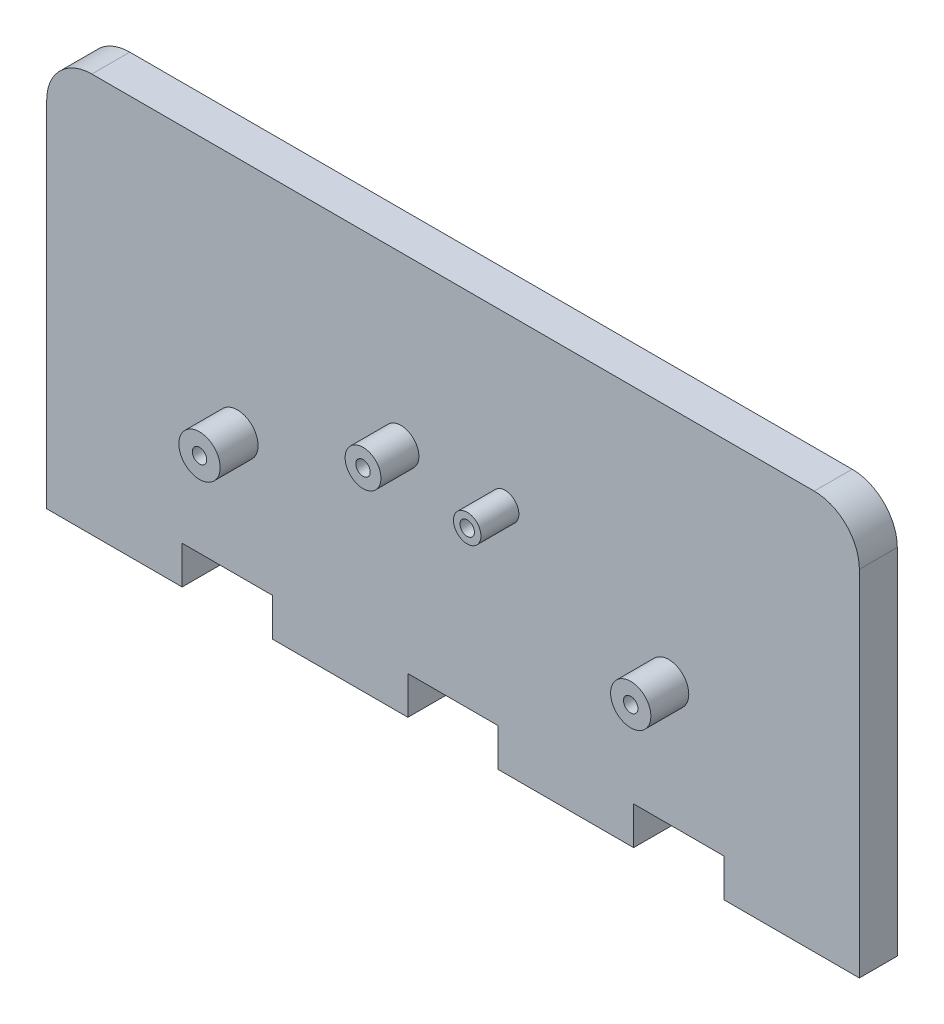
SolidWorks part; units mm, degrees
material "Teak"
ref_plane "Front Plane" through (0, 0, 0) normal (0, 0, 1) x (1, 0, 0)
ref_plane "Top Plane" through (0, 0, 0) normal (0, 1, 0) x (1, 0, 0)
ref_plane "Right Plane" through (0, 0, 0) normal (1, 0, 0) x (0, 0, -1)
sketch "Sketch1" plane through (0, 0, 0) normal (0, 0, 1) x (1, 0, 0)
  line L1 (-30.5325, 25.3111) -> (83.7675, 25.3111)
  line L2 (-30.5325, 25.3111) -> (-30.5325, -30.8229)
  line L3 (-30.5325, -30.8229) -> (83.7675, -30.8229)
  line L4 (83.7675, 25.3111) -> (83.7675, -30.8229)
  dimension "D1" = 56.134
  dimension "D2" = 114.3
extrude "Boss-Extrude1" add sketch "Sketch1" along normal blind 5.334 contours L1 L4 L3 L2
sketch "Sketch2" plane through (0, 0, 5.334) normal (0, 0, 1) x (1, 0, 0)
  line L0 (-30.5325, -30.8229) -> (83.7675, -30.8229) construction
  line L1 (-11.4825, -30.8229) -> (1.2175, -30.8229)
  line L2 (-11.4825, -30.8229) -> (-11.4825, -25.4889)
  line L3 (-11.4825, -25.4889) -> (1.2175, -25.4889)
  line L4 (1.2175, -30.8229) -> (1.2175, -25.4889)
  line L5 (-11.4825, -25.4889) -> (-30.5325, -25.4889) construction
  line L6 (20.2675, -30.8229) -> (32.9675, -30.8229)
  line L7 (20.2675, -30.8229) -> (20.2675, -25.4889)
  line L8 (20.2675, -25.4889) -> (32.9675, -25.4889)
  line L9 (32.9675, -30.8229) -> (32.9675, -25.4889)
  line L10 (52.0175, -30.8229) -> (64.7175, -30.8229)
  line L11 (52.0175, -30.8229) -> (52.0175, -25.4889)
  line L12 (52.0175, -25.4889) -> (64.7175, -25.4889)
  line L13 (64.7175, -30.8229) -> (64.7175, -25.4889)
  line L14 (-30.5325, 25.3111) -> (-30.5325, -30.8229) construction
  line L15 (1.2175, -25.4889) -> (20.2675, -25.4889) construction
  line L16 (32.9675, -25.4889) -> (52.0175, -25.4889) construction
  line L17 (64.7175, -25.4889) -> (83.7675, -25.4889) construction
  line L18 (83.7675, 25.3111) -> (83.7675, -30.8229) construction
  dimension "D1" = 19.05
  dimension "D2" = 12.7
  dimension "D3" = 19.05
  dimension "D4" = 12.7
  dimension "D5" = 19.05
  dimension "D6" = 12.7
  dimension "D7" = 19.05
  dimension "D8" = 5.334
extrude "Cut-Extrude1" cut sketch "Sketch2" against normal through all
fillet "Fillet1" radius 6.35 2 edges at (83.7675, 25.3111, 2.667) (-30.5325, 25.3111, 2.667)
sketch "Sketch3" plane through (0, 0, 0) normal (0, 0, -1) x (-1, 0, 0)
  line L16 (24.1825, 25.3111) -> (-77.4175, 25.3111)
  line L17 (-83.7675, 18.9611) -> (-83.7675, -30.8229)
  line L18 (-83.7675, -30.8229) -> (-64.7175, -30.8229)
  line L19 (-64.7175, -30.8229) -> (-64.7175, -25.4889)
  line L20 (-64.7175, -25.4889) -> (-52.0175, -25.4889)
  line L21 (-52.0175, -25.4889) -> (-52.0175, -30.8229)
  line L22 (-52.0175, -30.8229) -> (-32.9675, -30.8229)
  line L23 (-32.9675, -30.8229) -> (-32.9675, -25.4889)
  line L24 (-32.9675, -25.4889) -> (-20.2675, -25.4889)
  line L25 (-20.2675, -25.4889) -> (-20.2675, -30.8229)
  line L26 (-20.2675, -30.8229) -> (-1.2175, -30.8229)
  line L27 (-1.2175, -30.8229) -> (-1.2175, -25.4889)
  line L28 (-1.2175, -25.4889) -> (11.4825, -25.4889)
  line L29 (11.4825, -25.4889) -> (11.4825, -30.8229)
  line L30 (11.4825, -30.8229) -> (30.5325, -30.8229)
  line L31 (30.5325, -30.8229) -> (30.5325, 18.9611)
  line L32 (24.1825, 25.3111) -> (-77.4175, 25.3111)
  line L33 (-83.7675, 18.9611) -> (-83.7675, -30.8229)
  line L34 (-83.7675, -30.8229) -> (-64.7175, -30.8229)
  line L35 (-64.7175, -30.8229) -> (-64.7175, -25.4889)
  line L36 (-64.7175, -25.4889) -> (-52.0175, -25.4889)
  line L37 (-52.0175, -25.4889) -> (-52.0175, -30.8229)
  line L38 (-52.0175, -30.8229) -> (-32.9675, -30.8229)
  line L39 (-32.9675, -30.8229) -> (-32.9675, -25.4889)
  line L40 (-32.9675, -25.4889) -> (-20.2675, -25.4889)
  line L41 (-20.2675, -25.4889) -> (-20.2675, -30.8229)
  line L42 (-20.2675, -30.8229) -> (-1.2175, -30.8229)
  line L43 (-1.2175, -30.8229) -> (-1.2175, -25.4889)
  line L44 (-1.2175, -25.4889) -> (11.4825, -25.4889)
  line L45 (11.4825, -25.4889) -> (11.4825, -30.8229)
  line L46 (11.4825, -30.8229) -> (30.5325, -30.8229)
  line L47 (30.5325, -30.8229) -> (30.5325, 18.9611)
  line L48 (-83.7675, 18.9611) -> (-83.7675, -30.8229)
  line L49 (24.1825, 25.3111) -> (-77.4175, 25.3111)
  line L50 (30.5325, -30.8229) -> (30.5325, 18.9611)
  line L51 (11.4825, -30.8229) -> (30.5325, -30.8229)
  line L52 (11.4825, -25.4889) -> (11.4825, -30.8229)
  line L53 (-1.2175, -25.4889) -> (11.4825, -25.4889)
  line L54 (-1.2175, -30.8229) -> (-1.2175, -25.4889)
  line L55 (-20.2675, -30.8229) -> (-1.2175, -30.8229)
  line L56 (-20.2675, -25.4889) -> (-20.2675, -30.8229)
  line L57 (-32.9675, -25.4889) -> (-20.2675, -25.4889)
  line L58 (-32.9675, -30.8229) -> (-32.9675, -25.4889)
  line L59 (-52.0175, -30.8229) -> (-32.9675, -30.8229)
  line L60 (-52.0175, -25.4889) -> (-52.0175, -30.8229)
  line L61 (-64.7175, -25.4889) -> (-52.0175, -25.4889)
  line L62 (-64.7175, -30.8229) -> (-64.7175, -25.4889)
  line L63 (-83.7675, -30.8229) -> (-64.7175, -30.8229)
  line L64 (-83.7675, 18.9611) -> (-83.7675, -30.8229)
  line L65 (24.1825, 25.3111) -> (-77.4175, 25.3111)
  line L66 (30.5325, -30.8229) -> (30.5325, 18.9611)
  line L67 (11.4825, -30.8229) -> (30.5325, -30.8229)
  line L68 (11.4825, -25.4889) -> (11.4825, -30.8229)
  line L69 (-1.2175, -25.4889) -> (11.4825, -25.4889)
  line L70 (-1.2175, -30.8229) -> (-1.2175, -25.4889)
  line L71 (-20.2675, -30.8229) -> (-1.2175, -30.8229)
  line L72 (-20.2675, -25.4889) -> (-20.2675, -30.8229)
  line L73 (-32.9675, -25.4889) -> (-20.2675, -25.4889)
  line L74 (-32.9675, -30.8229) -> (-32.9675, -25.4889)
  line L75 (-52.0175, -30.8229) -> (-32.9675, -30.8229)
  line L76 (-52.0175, -25.4889) -> (-52.0175, -30.8229)
  line L77 (-64.7175, -25.4889) -> (-52.0175, -25.4889)
  line L78 (-64.7175, -30.8229) -> (-64.7175, -25.4889)
  line L79 (-83.7675, -30.8229) -> (-64.7175, -30.8229)
  circle A0 centre (3.7085, -8.2649) radius 1.5 construction
  circle A1 centre (-19.2915, 1.7351) radius 1.5 construction
  arc A2 (-77.4175, 25.3111) -> (-83.7675, 18.9611) centre (-77.4175, 18.9611) ccw
  arc A3 (30.5325, 18.9611) -> (24.1825, 25.3111) centre (24.1825, 18.9611) ccw
  arc A4 (-77.4175, 25.3111) -> (-83.7675, 18.9611) centre (-77.4175, 18.9611) ccw
  arc A5 (30.5325, 18.9611) -> (24.1825, 25.3111) centre (24.1825, 18.9611) ccw
  arc A6 (-77.4175, 25.3111) -> (-83.7675, 18.9611) centre (-77.4175, 18.9611) ccw
  arc A7 (30.5325, 18.9611) -> (24.1825, 25.3111) centre (24.1825, 18.9611) ccw
  arc A8 (-77.4175, 25.3111) -> (-83.7675, 18.9611) centre (-77.4175, 18.9611) ccw
  arc A9 (30.5325, 18.9611) -> (24.1825, 25.3111) centre (24.1825, 18.9611) ccw
  circle A10 centre (-56.9435, -8.2649) radius 1.5 construction
  circle A11 centre (-33.9435, 1.7351) radius 1.5 construction
  circle A12 centre (3.7085, -8.2649) radius 1.5
  circle A13 centre (-19.2915, 1.7351) radius 1.5
  circle A14 centre (-56.9435, -8.2649) radius 1.5
  circle A15 centre (-33.9435, 1.7351) radius 1.5
  dimension "D1" = 0
  dimension "D2" = 0
extrude "Cut-Extrude2" cut sketch "Sketch3" against normal through all contours A12 | A13 | A14 | A15
sketch "Sketch4" plane through (0, 0, 5.334) normal (0, 0, 1) x (1, 0, 0)
  circle A0 centre (-3.7085, -8.2649) radius 1.016
  circle A1 centre (-3.7085, -8.2649) radius 2.9039
extrude "Boss-Extrude2" add sketch "Sketch4" along normal blind 5.334
sketch "Sketch5" plane through (0, 0, 5.334) normal (0, 0, 1) x (1, 0, 0)
  circle A0 centre (19.2915, 1.7351) radius 1.016
  circle A1 centre (19.2915, 1.7351) radius 2.5191
extrude "Boss-Extrude3" add sketch "Sketch5" along normal blind 5.334
sketch "Sketch6" plane through (0, 0, 5.334) normal (0, 0, 1) x (1, 0, 0)
  circle A0 centre (33.9435, 1.7351) radius 1.016
  circle A1 centre (33.9435, 1.7351) radius 1.9323
extrude "Boss-Extrude4" add sketch "Sketch6" along normal blind 5.334
sketch "Sketch7" plane through (0, 0, 5.334) normal (0, 0, 1) x (1, 0, 0)
  circle A0 centre (56.9435, -8.2649) radius 1.016
  circle A1 centre (56.9435, -8.2649) radius 2.8308
extrude "Boss-Extrude5" add sketch "Sketch7" along normal blind 5.334
equation "\"MDF\"= .21in"
equation "\"Foamcore\"= .13in"
equation "\"Gmaterial\"= \"MDF\""
equation "\"D1@Sketch1\"=\"MDF\"+2"
equation "\"D1@Boss-Extrude1\"=\"MDF\""
equation "\"D8@Sketch2\"=\"MDF\""
equation "\"D1@Boss-Extrude2\"=\"MDF\""
